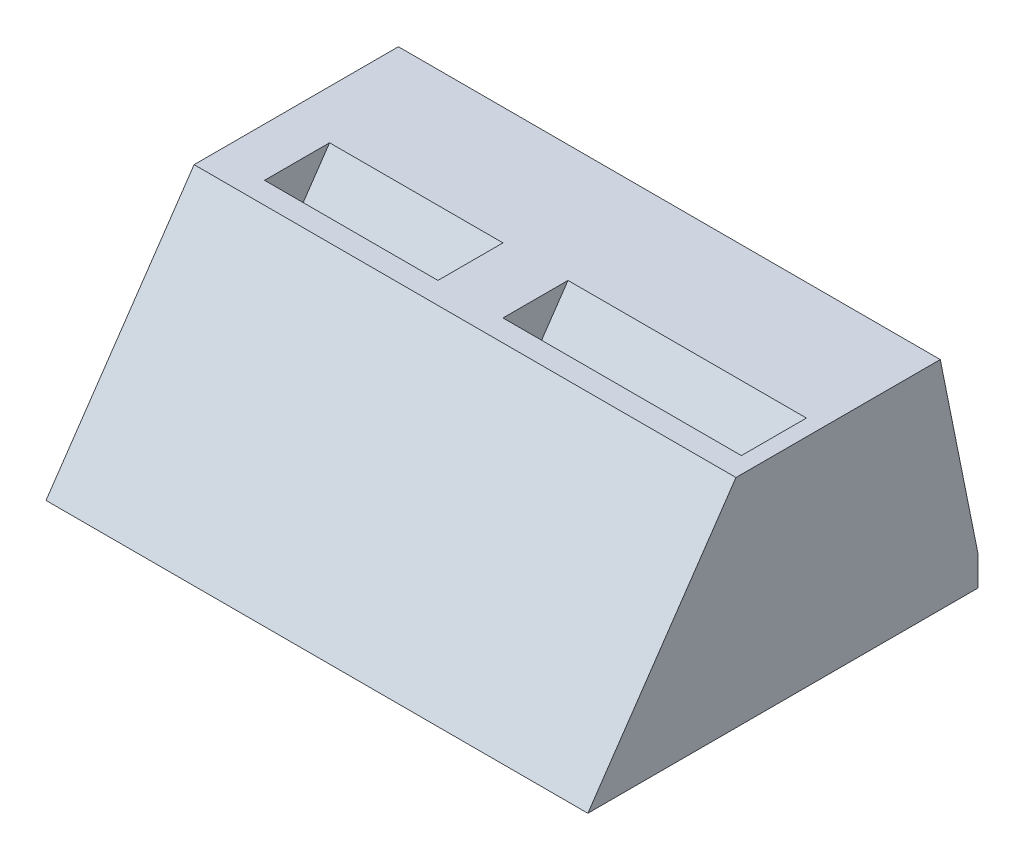
SolidWorks part; units mm, degrees
ref_plane "Ebene vorne" through (0, 0, 0) normal (0, 0, 1) x (1, 0, 0)
ref_plane "Ebene oben" through (0, 0, 0) normal (0, 1, 0) x (1, 0, 0)
ref_plane "Ebene rechts" through (0, 0, 0) normal (1, 0, 0) x (0, 0, -1)
sketch "Skizze1" plane through (0, 0, 0) normal (0, 0, 1) x (1, 0, 0)
  line L1 (-25, -15) -> (25, -15)
  line L2 (-25, -15) -> (-25, 15)
  line L3 (-25, 15) -> (25, 15)
  line L4 (25, -15) -> (25, 15)
  line L5 (-25, -15) -> (25, 15) construction
  line L6 (-25, 15) -> (25, -15) construction
  point P0 (0, 0)
  dimension "D1" = 50
  dimension "D2" = 30
extrude "Aufsatz-Linear austragen1" add sketch "Skizze1" along normal blind 40
ref_plane "Ebene1" through (0, 0, 0) normal (-1, 0, 0) x (0, 0, 1)
sketch "Skizze2" plane through (0, 0, 0) normal (-1, 0, 0) x (0, 0, 1)
  line L0 (7.5, 15) -> (28, -15)
  line L1 (40, 15) -> (0, 15) construction
  line L2 (40, -15) -> (0, -15) construction
  line L3 (28, -15) -> (34, -15)
  line L4 (34, -15) -> (13.5, 15)
  line L5 (13.5, 15) -> (7.5, 15)
  line L6 (40, 15) -> (40, -15) construction
  line L8 (26.6333, -13) -> (32.6333, -13)
  dimension "D1" = 6
  dimension "D2" = 6
  dimension "D3" = 7.5
  dimension "D4" = 2
extrude "FPV_Sender" cut sketch "Skizze2" against normal blind 22 from offset 1.5 contours L0 L8 L4 L5 region at (0, 1, 20.0667) offset against normal yes
sketch "Skizze4" plane through (0, 0, 0) normal (-1, 0, 0) x (0, 0, 1)
  line L0 (13.5, 15) -> (7.5, 15)
  line L1 (7.5, 15) -> (26.6333, -13)
  line L2 (7.5, 15) -> (26.6333, -13) construction
  line L3 (26.6333, -13) -> (32.6333, -13)
  line L4 (32.6333, -13) -> (13.5, 15) construction
  line L5 (32.6333, -13) -> (13.5, 15)
  dimension "D1" = 28
extrude "Empfänger" cut sketch "Skizze4" along normal blind 16 from offset 4.5
sketch "Skizze5" plane through (-25, 0, 0) normal (-1, 0, 0) x (0, 0, 1)
  line L0 (15.5, 15) -> (40, 15)
  line L1 (40, 15) -> (0, 15) construction
  line L2 (40, 15) -> (40, -20.8537)
  line L3 (40, 15) -> (40, -15) construction
  line L4 (40, -20.8537) -> (15.5, 15)
  line L5 (32.6333, -13) -> (13.5, 15) construction
  line L6 (5.5, 15) -> (0, -12.25)
  line L7 (0, 15) -> (0, -15) construction
  line L8 (0, -12.25) -> (0, 15)
  line L9 (0, 15) -> (5.5, 15)
  line L10 (40, -15) -> (0, -15) construction
  dimension "D1" = 2
  dimension "D2" = 2.75
  dimension "D3" = 2
extrude "Schnitt-Linear austragen3" cut sketch "Skizze5" against normal through all and the other way through all
sketch "Skizze7" plane through (25, 0, 0) normal (1, 0, 0) x (0, 0, -1)
  line L0 (-5.5, 15) -> (-15.5, 15)
  line L1 (-15.5, 15) -> (-22.3333, 5)
  line L2 (-15.5, 15) -> (-36, -15) construction
  line L3 (-22.3333, 5) -> (-3.4817, 5)
  line L4 (0, -12.25) -> (-5.5, 15) construction
  line L5 (-3.4817, 5) -> (-5.5, 15)
  dimension "D1" = 10
extrude "Schnitt-Linear austragen5" cut sketch "Skizze7" against normal up to surface (50 mm away) up to face at (-25, 0.55, 11.95)
shell "Wandung2" thickness 2 removed face at (0, -15, 18)
sketch "Skizze6" plane through (0, -13, 0) normal (0, 1, 0) x (1, 0, 0)
  line L0 (23.5, -26.6333) -> (1.5, -26.6333) construction
  line L1 (1.5, -32.6333) -> (8.5, -32.6333)
  line L2 (1.5, -32.6333) -> (1.5, -26.6333)
  line L3 (1.5, -26.6333) -> (8.5, -26.6333)
  line L4 (8.5, -32.6333) -> (8.5, -26.6333)
  dimension "D1" = 7
extrude "Schnitt-Linear austragen4" cut sketch "Skizze6" against normal up to surface (2 mm away) up to face at (-5.1, -15, 24.0621)
